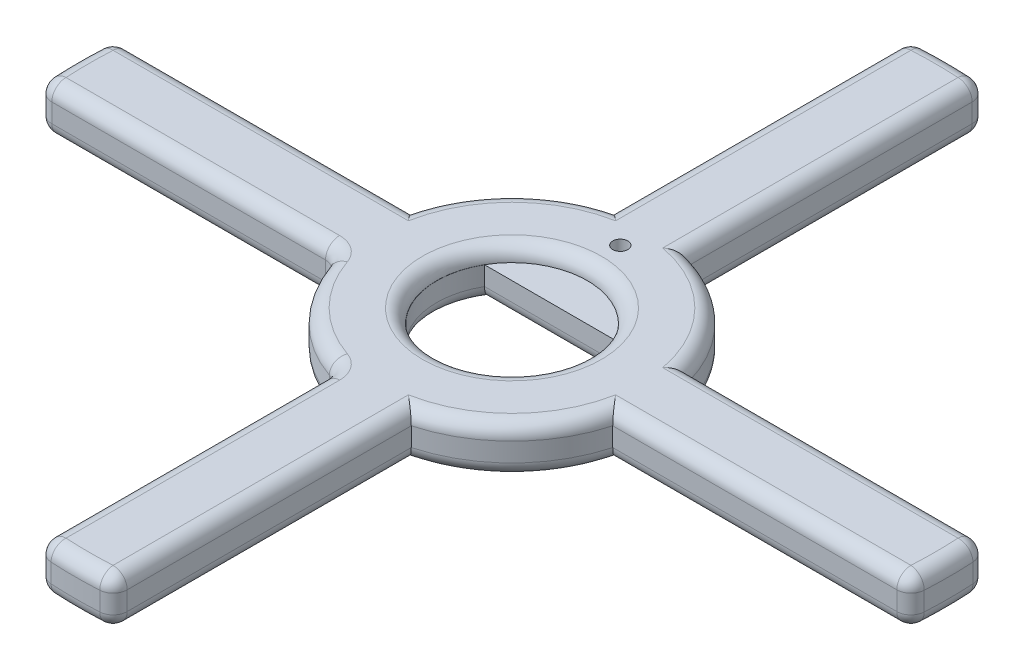
SolidWorks part; units mm, degrees
ref_plane "Front Plane" through (0, 0, 0) normal (0, 0, 1) x (1, 0, 0)
ref_plane "Top Plane" through (0, 0, 0) normal (0, 1, 0) x (1, 0, 0)
ref_plane "Right Plane" through (0, 0, 0) normal (1, 0, 0) x (0, 0, -1)
sketch "Sketch1" plane through (0, 0, 0) normal (0, 1, 0) x (1, 0, 0)
  line L0 (-13.8191, 8) -> (13.8191, 8)
  line L1 (0, 0) -> (121.2616, 0) construction
  line L2 (29.3909, 8) -> (92.4938, 8)
  line L3 (29.3909, -8) -> (92.4938, -8)
  line L4 (8, -29.3909) -> (8, -92.4938)
  line L5 (-8, -29.3909) -> (-8, -92.4938)
  line L6 (-29.3909, -8) -> (-92.4938, -8)
  line L7 (-29.3909, 8) -> (-92.4938, 8)
  line L8 (-8, 29.3909) -> (-8, 92.4938)
  line L9 (8, 29.3909) -> (8, 92.4938)
  circle A0 centre (0, 0) radius 15.9677 construction
  arc A1 (-13.8191, 8) -> (13.8191, 8) centre (0, 0) ccw
  circle A2 centre (0, 0) radius 92.8391 construction
  arc A3 (92.4938, 8) -> (92.4938, -8) centre (0, 0) cw
  circle A4 centre (0, 0) radius 30.4602 construction
  arc A5 (8, -92.4938) -> (-8, -92.4938) centre (0, 0) cw
  arc A6 (-92.4938, -8) -> (-92.4938, 8) centre (0, 0) cw
  arc A7 (-8, 92.4938) -> (8, 92.4938) centre (0, 0) cw
  arc A8 (29.3909, 8) -> (8, 29.3909) centre (0, 0) ccw
  arc A9 (-8, 29.3909) -> (-29.3909, 8) centre (0, 0) ccw
  arc A10 (-29.3909, -8) -> (-8, -29.3909) centre (0, 0) ccw
  arc A11 (8, -29.3909) -> (29.3909, -8) centre (0, 0) ccw
  point P27 (0, 0)
  point P40 (0, 0)
  dimension "D1" = 8
  dimension "D2" = 8
  dimension "D3" = 4
extrude "Boss-Extrude2" add sketch "Sketch1" along normal blind 10
sketch "Sketch2" plane through (0, 10, 0) normal (0, 1, 0) x (1, 0, 0)
  circle A0 centre (0, 0) radius 16
extrude "Cut-Extrude1" cut sketch "Sketch2" against normal blind 3
fillet "Fillet4" radius 3 45 edges at (-8, 5, 92.4938) (8, 5, 92.4938) (92.4938, 5, 8) (92.4938, 5, -8) (8, 5, -92.4938) (-8, 5, -92.4938) (0, 0, -8) (0, 0, 15.9677) (8, 0, -60.9423) (0, 0, -92.8391) (-8, 0, -60.9423) (-21.5386, 0, -21.5386) (-60.9423, 0, -8) (-60.9423, 0, 8) (-8, 0, 60.9423) (0, 0, 92.8391) (8, 0, 60.9423) (21.5386, 0, 21.5386) (60.9423, 0, 8) (92.8391, 0, 0) (60.9423, 0, -8) (21.5386, 0, -21.5386) (-92.4938, 5, -8) (-92.4938, 5, 8) (-92.8391, 0, 0) (-29.3909, 5, 8) (-8, 5, 29.3909) (-21.5386, 0, 21.5386) (60.9423, 10, -8) (92.8391, 10, 0) (60.9423, 10, 8) (21.5386, 10, 21.5386) (8, 10, 60.9423) (0, 10, 92.8391) (-8, 10, 60.9423) (-21.5386, 10, 21.5386) (-60.9423, 10, 8) (-92.8391, 10, 0) (-60.9423, 10, -8) (-21.5386, 10, -21.5386) (-8, 10, -60.9423) (0, 10, -92.8391) (8, 10, -60.9423) (21.5386, 10, -21.5386) (0, 10, 16)
sketch "Sketch3" plane through (0, 0, 0) normal (0, -1, 0) x (-1, 0, 0)
  circle A0 centre (0, 23) radius 1.6
extrude "Cut-Extrude2" cut sketch "Sketch3" against normal through all
